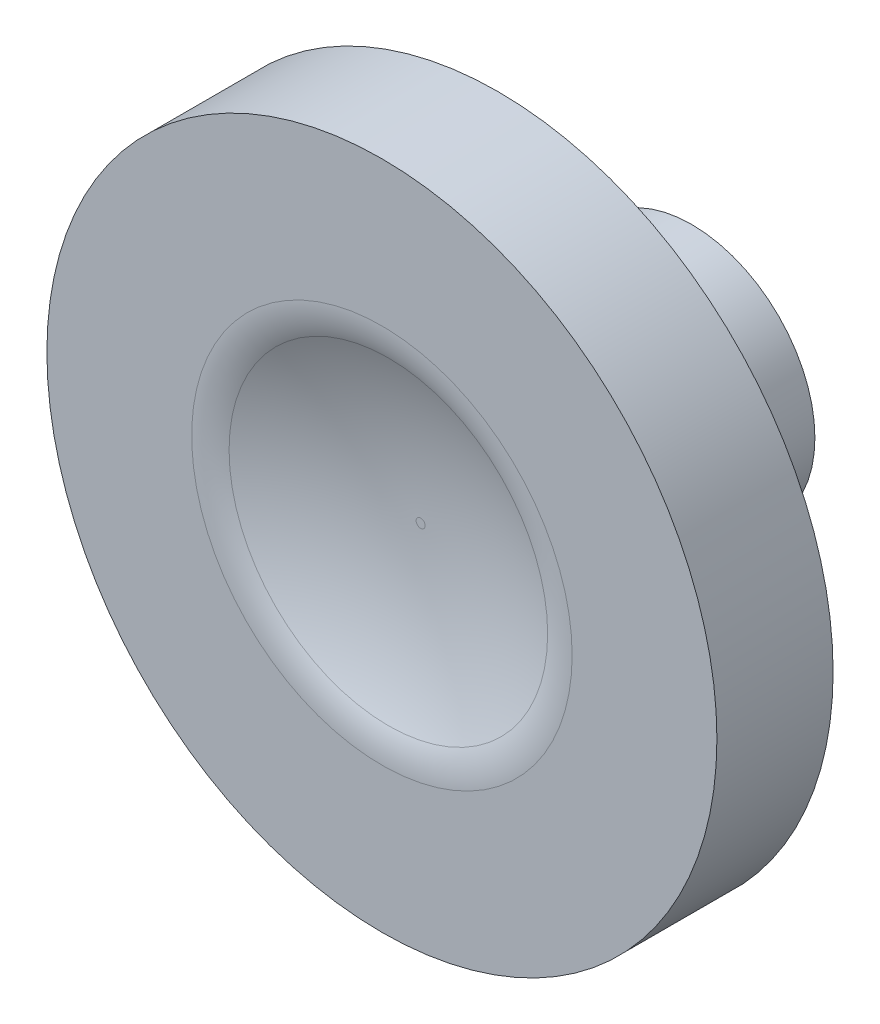
SolidWorks part; units mm, degrees
ref_plane "Front Plane" through (0, 0, 0) normal (0, 0, 1) x (1, 0, 0)
ref_plane "Top Plane" through (0, 0, 0) normal (0, 1, 0) x (1, 0, 0)
ref_plane "Right Plane" through (0, 0, 0) normal (1, 0, 0) x (0, 0, -1)
sketch "Sketch1" plane through (0, 0, 0) normal (0, 0, 1) x (1, 0, 0)
  circle A0 centre (0, 0) radius 10.9855
  circle A1 centre (0, 0) radius 4.0386
  dimension "D1" = 21.971
  dimension "D2" = 8.0772
extrude "Boss-Extrude1" add sketch "Sketch1" along normal blind 2.54 contours A1
extrude "Boss-Extrude2" add sketch "Sketch1<4>" along normal blind 3.81
sketch "Sketch1<4>" plane through (0, 0, 0) normal (0, 0, 1) x (1, 0, 0) same geometry as "Sketch1"
fillet "Fillet1" radius 2.54 1 edges at (4.0386, 0, 3.81)
fillet "Fillet2" radius 12.7 1 edges at (4.0386, 0, 2.54)
sketch "Sketch2" plane through (0, 0, 0) normal (0, 0, -1) x (-1, 0, 0)
extrude "Boss-Extrude3" add sketch "Sketch1<6>" against normal blind 6.35 contours A1
sketch "Sketch1<6>" plane through (0, 0, 0) normal (0, 0, 1) x (1, 0, 0) same geometry as "Sketch1"
sketch "Sketch3" plane through (0, 0, -6.35) normal (0, 0, -1) x (-1, 0, 0)
  circle A0 centre (0, 0) radius 2.54
  dimension "D1" = 5.08
extrude "Cut-Extrude1" cut sketch "Sketch3" against normal blind 3.81
